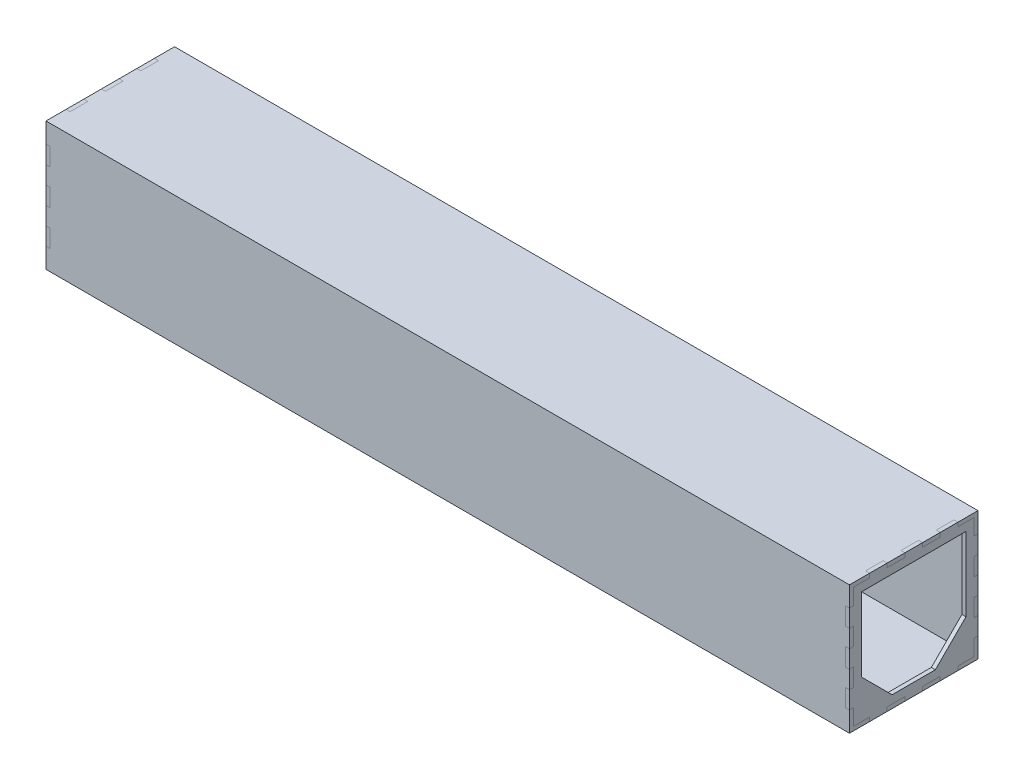
SolidWorks part; units mm, degrees
ref_plane "Front Plane" through (0, 0, 0) normal (0, 0, 1) x (1, 0, 0)
ref_plane "Top Plane" through (0, 0, 0) normal (0, 1, 0) x (1, 0, 0)
ref_plane "Right Plane" through (0, 0, 0) normal (1, 0, 0) x (0, 0, -1)
sketch "Sketch1" plane through (0, 0, 0) normal (1, 0, 0) x (0, 0, -1)
  line L0 (-98.425, 3.175) -> (-98.425, 98.425)
  line L1 (0, 0) -> (-101.6, 0)
  line L2 (0, 0) -> (0, 101.6)
  line L3 (0, 101.6) -> (-101.6, 101.6)
  line L4 (-101.6, 0) -> (-101.6, 101.6)
  line L5 (-3.175, 98.425) -> (-98.425, 98.425)
  line L6 (-3.175, 3.175) -> (-3.175, 98.425)
  line L7 (-3.175, 3.175) -> (-98.425, 3.175)
  dimension "D1" = 101.6
  dimension "D2" = 101.6
  dimension "D3" = 3.175
extrude "Boss-Extrude1" add sketch "Sketch1" along normal blind 628.65
sketch "Sketch3" plane through (0, 0, 0) normal (-1, 0, 0) x (0, 0, 1)
  line L0 (0, 85.725) -> (3.175, 85.725)
  line L1 (0, 0) -> (0, 101.6) construction
  line L2 (3.175, 3.175) -> (3.175, 98.425) construction
  line L3 (15.875, 101.6) -> (15.875, 98.425)
  line L4 (0, 101.6) -> (101.6, 101.6) construction
  line L5 (3.175, 98.425) -> (98.425, 98.425) construction
  line L6 (3.175, 50.8) -> (50.8, 50.8) construction
  line L7 (29.845, 101.6) -> (29.845, 98.425)
  line L8 (43.815, 101.6) -> (43.815, 98.425)
  line L9 (3.175, 98.425) -> (50.8, 50.8) construction
  line L10 (50.8, 50.8) -> (50.8, 98.425) construction
  line L11 (0, 57.785) -> (3.175, 57.785)
  line L12 (0, 71.755) -> (3.175, 71.755)
  line L13 (0, 85.725) -> (0, 101.6)
  line L14 (0, 101.6) -> (15.875, 101.6)
  line L15 (3.175, 85.725) -> (3.175, 98.425)
  line L16 (3.175, 98.425) -> (15.875, 98.425)
  line L17 (29.845, 101.6) -> (43.815, 101.6)
  line L18 (29.845, 98.425) -> (43.815, 98.425)
  line L19 (0, 71.755) -> (0, 57.785)
  line L20 (3.175, 71.755) -> (3.175, 57.785)
  line L21 (98.425, 71.755) -> (98.425, 57.785)
  line L22 (101.6, 71.755) -> (101.6, 57.785)
  line L23 (71.755, 98.425) -> (57.785, 98.425)
  line L24 (71.755, 101.6) -> (57.785, 101.6)
  line L25 (98.425, 98.425) -> (85.725, 98.425)
  line L26 (98.425, 85.725) -> (98.425, 98.425)
  line L27 (101.6, 101.6) -> (85.725, 101.6)
  line L28 (101.6, 85.725) -> (101.6, 101.6)
  line L29 (101.6, 71.755) -> (98.425, 71.755)
  line L30 (101.6, 57.785) -> (98.425, 57.785)
  line L31 (57.785, 101.6) -> (57.785, 98.425)
  line L32 (71.755, 101.6) -> (71.755, 98.425)
  line L33 (85.725, 101.6) -> (85.725, 98.425)
  line L34 (101.6, 85.725) -> (98.425, 85.725)
  line L35 (101.6, 15.875) -> (98.425, 15.875)
  line L36 (85.725, 0) -> (85.725, 3.175)
  line L37 (71.755, 0) -> (71.755, 3.175)
  line L38 (57.785, 0) -> (57.785, 3.175)
  line L39 (101.6, 43.815) -> (98.425, 43.815)
  line L40 (101.6, 29.845) -> (98.425, 29.845)
  line L41 (101.6, 15.875) -> (101.6, 0)
  line L42 (101.6, 0) -> (85.725, 0)
  line L43 (98.425, 15.875) -> (98.425, 3.175)
  line L44 (98.425, 3.175) -> (85.725, 3.175)
  line L45 (71.755, 0) -> (57.785, 0)
  line L46 (71.755, 3.175) -> (57.785, 3.175)
  line L47 (101.6, 29.845) -> (101.6, 43.815)
  line L48 (98.425, 29.845) -> (98.425, 43.815)
  line L49 (3.175, 29.845) -> (3.175, 43.815)
  line L50 (0, 29.845) -> (0, 43.815)
  line L51 (29.845, 3.175) -> (43.815, 3.175)
  line L52 (29.845, 0) -> (43.815, 0)
  line L53 (3.175, 3.175) -> (15.875, 3.175)
  line L54 (3.175, 15.875) -> (3.175, 3.175)
  line L55 (0, 0) -> (15.875, 0)
  line L56 (0, 15.875) -> (0, 0)
  line L57 (0, 29.845) -> (3.175, 29.845)
  line L58 (0, 43.815) -> (3.175, 43.815)
  line L59 (43.815, 0) -> (43.815, 3.175)
  line L60 (29.845, 0) -> (29.845, 3.175)
  line L61 (15.875, 0) -> (15.875, 3.175)
  line L62 (0, 15.875) -> (3.175, 15.875)
  point P27 (50.8, 98.425)
  dimension "D1" = 12.7
  dimension "D2" = 12.7
  dimension "D3" = 13.97
  dimension "D4" = 13.97
  dimension "D5" = 45
extrude "Boss-Extrude3" add sketch "Sketch3" along normal blind 3.175
sketch "Sketch4" plane through (0, 0, 0) normal (-1, 0, 0) x (0, 0, 1)
  line L0 (29.845, 98.425) -> (29.845, 101.6) construction
  line L1 (29.845, 101.6) -> (15.875, 101.6) construction
  line L2 (15.875, 101.6) -> (15.875, 98.425) construction
  line L3 (15.875, 98.425) -> (29.845, 98.425) construction
  line L4 (57.785, 98.425) -> (57.785, 101.6) construction
  line L5 (57.785, 101.6) -> (43.815, 101.6) construction
  line L6 (43.815, 101.6) -> (43.815, 98.425) construction
  line L7 (43.815, 98.425) -> (57.785, 98.425) construction
  line L8 (85.725, 98.425) -> (85.725, 101.6) construction
  line L9 (85.725, 101.6) -> (71.755, 101.6) construction
  line L10 (71.755, 101.6) -> (71.755, 98.425) construction
  line L11 (71.755, 98.425) -> (85.725, 98.425) construction
  line L12 (101.6, 85.725) -> (98.425, 85.725) construction
  line L13 (98.425, 85.725) -> (98.425, 71.755) construction
  line L14 (98.425, 71.755) -> (101.6, 71.755) construction
  line L15 (101.6, 71.755) -> (101.6, 85.725) construction
  line L16 (98.425, 43.815) -> (101.6, 43.815) construction
  line L17 (101.6, 43.815) -> (101.6, 57.785) construction
  line L18 (101.6, 57.785) -> (98.425, 57.785) construction
  line L19 (98.425, 57.785) -> (98.425, 43.815) construction
  line L20 (98.425, 15.875) -> (101.6, 15.875) construction
  line L21 (101.6, 15.875) -> (101.6, 29.845) construction
  line L22 (101.6, 29.845) -> (98.425, 29.845) construction
  line L23 (98.425, 29.845) -> (98.425, 15.875) construction
  line L24 (85.725, 0) -> (85.725, 3.175) construction
  line L25 (85.725, 3.175) -> (71.755, 3.175) construction
  line L26 (71.755, 3.175) -> (71.755, 0) construction
  line L27 (71.755, 0) -> (85.725, 0) construction
  line L28 (57.785, 0) -> (57.785, 3.175) construction
  line L29 (57.785, 3.175) -> (43.815, 3.175) construction
  line L30 (43.815, 3.175) -> (43.815, 0) construction
  line L31 (43.815, 0) -> (57.785, 0) construction
  line L32 (15.875, 3.175) -> (15.875, 0) construction
  line L33 (15.875, 0) -> (29.845, 0) construction
  line L34 (29.845, 0) -> (29.845, 3.175) construction
  line L35 (29.845, 3.175) -> (15.875, 3.175) construction
  line L36 (0, 15.875) -> (3.175, 15.875) construction
  line L37 (3.175, 15.875) -> (3.175, 29.845) construction
  line L38 (3.175, 29.845) -> (0, 29.845) construction
  line L39 (0, 29.845) -> (0, 15.875) construction
  line L40 (3.175, 57.785) -> (0, 57.785) construction
  line L41 (0, 57.785) -> (0, 43.815) construction
  line L42 (0, 43.815) -> (3.175, 43.815) construction
  line L43 (3.175, 43.815) -> (3.175, 57.785) construction
  line L44 (0, 71.755) -> (3.175, 71.755) construction
  line L45 (3.175, 71.755) -> (3.175, 85.725) construction
  line L46 (3.175, 85.725) -> (0, 85.725) construction
  line L47 (0, 85.725) -> (0, 71.755) construction
  line L48 (3.175, 57.785) -> (3.175, 71.755) construction
  line L49 (3.175, 29.845) -> (3.175, 43.815) construction
  line L50 (3.175, 3.175) -> (3.175, 15.875) construction
  line L51 (15.875, 3.175) -> (3.175, 3.175) construction
  line L52 (43.815, 3.175) -> (29.845, 3.175) construction
  line L53 (71.755, 3.175) -> (57.785, 3.175) construction
  line L54 (98.425, 3.175) -> (85.725, 3.175) construction
  line L55 (98.425, 15.875) -> (98.425, 3.175) construction
  line L56 (98.425, 43.815) -> (98.425, 29.845) construction
  line L57 (98.425, 71.755) -> (98.425, 57.785) construction
  line L58 (98.425, 98.425) -> (98.425, 85.725) construction
  line L59 (85.725, 98.425) -> (98.425, 98.425) construction
  line L60 (57.785, 98.425) -> (71.755, 98.425) construction
  line L61 (29.845, 98.425) -> (43.815, 98.425) construction
  line L62 (3.175, 98.425) -> (15.875, 98.425) construction
  line L63 (3.175, 85.725) -> (3.175, 98.425) construction
  line L64 (29.845, 98.425) -> (29.845, 101.6)
  line L65 (29.845, 101.6) -> (15.875, 101.6)
  line L66 (15.875, 101.6) -> (15.875, 98.425)
  line L67 (15.875, 98.425) -> (29.845, 98.425)
  line L68 (57.785, 98.425) -> (57.785, 101.6)
  line L69 (57.785, 101.6) -> (43.815, 101.6)
  line L70 (43.815, 101.6) -> (43.815, 98.425)
  line L71 (43.815, 98.425) -> (57.785, 98.425)
  line L72 (85.725, 98.425) -> (85.725, 101.6)
  line L73 (85.725, 101.6) -> (71.755, 101.6)
  line L74 (71.755, 101.6) -> (71.755, 98.425)
  line L75 (71.755, 98.425) -> (85.725, 98.425)
  line L76 (101.6, 85.725) -> (98.425, 85.725)
  line L77 (98.425, 85.725) -> (98.425, 71.755)
  line L78 (98.425, 71.755) -> (101.6, 71.755)
  line L79 (101.6, 71.755) -> (101.6, 85.725)
  line L80 (98.425, 43.815) -> (101.6, 43.815)
  line L81 (101.6, 43.815) -> (101.6, 57.785)
  line L82 (101.6, 57.785) -> (98.425, 57.785)
  line L83 (98.425, 57.785) -> (98.425, 43.815)
  line L84 (98.425, 15.875) -> (101.6, 15.875)
  line L85 (101.6, 15.875) -> (101.6, 29.845)
  line L86 (101.6, 29.845) -> (98.425, 29.845)
  line L87 (98.425, 29.845) -> (98.425, 15.875)
  line L88 (85.725, 0) -> (85.725, 3.175)
  line L89 (85.725, 3.175) -> (71.755, 3.175)
  line L90 (71.755, 3.175) -> (71.755, 0)
  line L91 (71.755, 0) -> (85.725, 0)
  line L92 (57.785, 0) -> (57.785, 3.175)
  line L93 (57.785, 3.175) -> (43.815, 3.175)
  line L94 (43.815, 3.175) -> (43.815, 0)
  line L95 (43.815, 0) -> (57.785, 0)
  line L96 (15.875, 3.175) -> (15.875, 0)
  line L97 (15.875, 0) -> (29.845, 0)
  line L98 (29.845, 0) -> (29.845, 3.175)
  line L99 (29.845, 3.175) -> (15.875, 3.175)
  line L100 (0, 15.875) -> (3.175, 15.875)
  line L101 (3.175, 15.875) -> (3.175, 29.845)
  line L102 (3.175, 29.845) -> (0, 29.845)
  line L103 (0, 29.845) -> (0, 15.875)
  line L104 (3.175, 57.785) -> (0, 57.785)
  line L105 (0, 57.785) -> (0, 43.815)
  line L106 (0, 43.815) -> (3.175, 43.815)
  line L107 (3.175, 43.815) -> (3.175, 57.785)
  line L108 (0, 71.755) -> (3.175, 71.755)
  line L109 (3.175, 71.755) -> (3.175, 85.725)
  line L110 (3.175, 85.725) -> (0, 85.725)
  line L111 (0, 85.725) -> (0, 71.755)
  line L112 (3.175, 57.785) -> (3.175, 71.755)
  line L113 (3.175, 29.845) -> (3.175, 43.815)
  line L114 (3.175, 3.175) -> (3.175, 15.875)
  line L115 (15.875, 3.175) -> (3.175, 3.175)
  line L116 (43.815, 3.175) -> (29.845, 3.175)
  line L117 (71.755, 3.175) -> (57.785, 3.175)
  line L118 (98.425, 3.175) -> (85.725, 3.175)
  line L119 (98.425, 15.875) -> (98.425, 3.175)
  line L120 (98.425, 43.815) -> (98.425, 29.845)
  line L121 (98.425, 71.755) -> (98.425, 57.785)
  line L122 (98.425, 98.425) -> (98.425, 85.725)
  line L123 (85.725, 98.425) -> (98.425, 98.425)
  line L124 (57.785, 98.425) -> (71.755, 98.425)
  line L125 (29.845, 98.425) -> (43.815, 98.425)
  line L126 (3.175, 98.425) -> (15.875, 98.425)
  line L127 (3.175, 85.725) -> (3.175, 98.425)
  line L129 (3.175, 98.425) -> (98.425, 98.425)
  line L130 (3.175, 98.425) -> (3.175, 3.175)
  line L131 (3.175, 3.175) -> (98.425, 3.175)
  line L132 (98.425, 98.425) -> (98.425, 3.175)
  line M5 (0, 71.755) -> (3.175, 71.755)
  line M6 (3.175, 71.755) -> (3.175, 85.725)
  line M7 (3.175, 85.725) -> (0, 85.725)
  line M8 (0, 85.725) -> (0, 71.755)
extrude "Boss-Extrude4" add sketch "Sketch4" along normal blind 3.175 separate body contours L66 L67 L64 L65 | L127 L112 L107 L113 L101 L114 L115 L99 L116 L93 L117 L89 L118 L119 L87 L120 L83 L121 L77 L122 L123 L75 L124 L71 L125 L67 L126 M6 | L70 L71 L68 L69 | L74 L75 L72 L73 | L78 L79 L76 L77 | L82 L83 L80 L81 | L86 L87 L84 L85 | L90 L91 L88 L89 | L94 L95 L92 L93 | L98 L99 L96 L97 | L102 L103 L100 L101 | L106 L107 L104 L105 | M8 M5 M6 M7 region at (0, 100.0125, 22.86) region at (0, 50.8, 50.8) region at (0, 100.0125, 50.8) region at (0, 78.74, 1.5875) region at (0, 100.0125, 78.74) region at (0, 50.8, 1.5875) region at (0, 78.74, 100.0125) region at (0, 22.86, 1.5875) region at (0, 50.8, 100.0125) region at (0, 1.5875, 22.86) region at (0, 22.86, 100.0125) region at (0, 1.5875, 50.8) region at (0, 1.5875, 78.74)
sketch "Sketch5" plane through (628.65, 0, 0) normal (1, 0, 0) x (0, 0, -1)
  line L0 (-92.075, 33.7033) -> (-67.8967, 9.525)
  line L1 (-92.075, 92.075) -> (-9.525, 92.075)
  line L2 (-92.075, 92.075) -> (-92.075, 9.525) construction
  line L3 (-92.075, 9.525) -> (-9.525, 9.525) construction
  line L4 (-9.525, 92.075) -> (-9.525, 9.525) construction
  line L5 (-33.7033, 9.525) -> (-9.525, 33.7033)
  line L6 (-67.8967, 9.525) -> (-33.7033, 9.525)
  line L7 (-92.075, 33.7033) -> (-92.075, 92.075)
  line L8 (-9.525, 92.075) -> (-9.525, 33.7033)
  line L52 (-15.875, 98.425) -> (-15.875, 101.6)
  line L53 (-3.175, 98.425) -> (-15.875, 98.425)
  line L54 (-3.175, 85.725) -> (-3.175, 98.425)
  line L55 (0, 85.725) -> (-3.175, 85.725)
  line L56 (0, 71.755) -> (0, 85.725)
  line L57 (-3.175, 71.755) -> (0, 71.755)
  line L58 (-3.175, 57.785) -> (-3.175, 71.755)
  line L59 (0, 57.785) -> (-3.175, 57.785)
  line L60 (0, 43.815) -> (0, 57.785)
  line L61 (-3.175, 43.815) -> (0, 43.815)
  line L62 (-3.175, 29.845) -> (-3.175, 43.815)
  line L63 (0, 29.845) -> (-3.175, 29.845)
  line L64 (0, 15.875) -> (0, 29.845)
  line L65 (-3.175, 15.875) -> (0, 15.875)
  line L66 (-3.175, 3.175) -> (-3.175, 15.875)
  line L67 (-15.875, 3.175) -> (-3.175, 3.175)
  line L68 (-15.875, 0) -> (-15.875, 3.175)
  line L69 (-29.845, 0) -> (-15.875, 0)
  line L70 (-29.845, 3.175) -> (-29.845, 0)
  line L71 (-43.815, 3.175) -> (-29.845, 3.175)
  line L72 (-43.815, 0) -> (-43.815, 3.175)
  line L73 (-57.785, 0) -> (-43.815, 0)
  line L74 (-57.785, 3.175) -> (-57.785, 0)
  line L75 (-71.755, 3.175) -> (-57.785, 3.175)
  line L76 (-71.755, 0) -> (-71.755, 3.175)
  line L77 (-85.725, 0) -> (-71.755, 0)
  line L78 (-85.725, 3.175) -> (-85.725, 0)
  line L79 (-98.425, 3.175) -> (-85.725, 3.175)
  line L80 (-98.425, 15.875) -> (-98.425, 3.175)
  line L81 (-101.6, 15.875) -> (-98.425, 15.875)
  line L82 (-101.6, 29.845) -> (-101.6, 15.875)
  line L83 (-98.425, 29.845) -> (-101.6, 29.845)
  line L84 (-98.425, 43.815) -> (-98.425, 29.845)
  line L85 (-101.6, 43.815) -> (-98.425, 43.815)
  line L86 (-101.6, 57.785) -> (-101.6, 43.815)
  line L87 (-98.425, 57.785) -> (-101.6, 57.785)
  line L88 (-98.425, 71.755) -> (-98.425, 57.785)
  line L89 (-101.6, 71.755) -> (-98.425, 71.755)
  line L90 (-101.6, 85.725) -> (-101.6, 71.755)
  line L91 (-98.425, 85.725) -> (-101.6, 85.725)
  line L92 (-98.425, 98.425) -> (-98.425, 85.725)
  line L93 (-85.725, 98.425) -> (-98.425, 98.425)
  line L94 (-85.725, 101.6) -> (-85.725, 98.425)
  line L95 (-71.755, 101.6) -> (-85.725, 101.6)
  line L96 (-71.755, 98.425) -> (-71.755, 101.6)
  line L97 (-57.785, 98.425) -> (-71.755, 98.425)
  line L98 (-57.785, 101.6) -> (-57.785, 98.425)
  line L99 (-43.815, 101.6) -> (-57.785, 101.6)
  line L100 (-43.815, 98.425) -> (-43.815, 101.6)
  line L101 (-29.845, 98.425) -> (-43.815, 98.425)
  line L102 (-29.845, 101.6) -> (-29.845, 98.425)
  line L103 (-15.875, 101.6) -> (-29.845, 101.6)
  line L104 (-15.875, 98.425) -> (-15.875, 101.6)
  line L105 (-3.175, 98.425) -> (-15.875, 98.425)
  line L106 (-3.175, 85.725) -> (-3.175, 98.425)
  line L107 (0, 85.725) -> (-3.175, 85.725)
  line L108 (0, 71.755) -> (0, 85.725)
  line L109 (-3.175, 71.755) -> (0, 71.755)
  line L110 (-3.175, 57.785) -> (-3.175, 71.755)
  line L111 (0, 57.785) -> (-3.175, 57.785)
  line L112 (0, 43.815) -> (0, 57.785)
  line L113 (-3.175, 43.815) -> (0, 43.815)
  line L114 (-3.175, 29.845) -> (-3.175, 43.815)
  line L115 (0, 29.845) -> (-3.175, 29.845)
  line L116 (0, 15.875) -> (0, 29.845)
  line L117 (-3.175, 15.875) -> (0, 15.875)
  line L118 (-3.175, 3.175) -> (-3.175, 15.875)
  line L119 (-15.875, 3.175) -> (-3.175, 3.175)
  line L120 (-15.875, 0) -> (-15.875, 3.175)
  line L121 (-29.845, 0) -> (-15.875, 0)
  line L122 (-29.845, 3.175) -> (-29.845, 0)
  line L123 (-43.815, 3.175) -> (-29.845, 3.175)
  line L124 (-43.815, 0) -> (-43.815, 3.175)
  line L125 (-57.785, 0) -> (-43.815, 0)
  line L126 (-57.785, 3.175) -> (-57.785, 0)
  line L127 (-71.755, 3.175) -> (-57.785, 3.175)
  line L128 (-71.755, 0) -> (-71.755, 3.175)
  line L129 (-85.725, 0) -> (-71.755, 0)
  line L130 (-85.725, 3.175) -> (-85.725, 0)
  line L131 (-98.425, 3.175) -> (-85.725, 3.175)
  line L132 (-98.425, 15.875) -> (-98.425, 3.175)
  line L133 (-101.6, 15.875) -> (-98.425, 15.875)
  line L134 (-101.6, 29.845) -> (-101.6, 15.875)
  line L135 (-98.425, 29.845) -> (-101.6, 29.845)
  line L136 (-98.425, 43.815) -> (-98.425, 29.845)
  line L137 (-101.6, 43.815) -> (-98.425, 43.815)
  line L138 (-101.6, 57.785) -> (-101.6, 43.815)
  line L139 (-98.425, 57.785) -> (-101.6, 57.785)
  line L140 (-98.425, 71.755) -> (-98.425, 57.785)
  line L141 (-101.6, 71.755) -> (-98.425, 71.755)
  line L142 (-101.6, 85.725) -> (-101.6, 71.755)
  line L143 (-98.425, 85.725) -> (-101.6, 85.725)
  line L144 (-98.425, 98.425) -> (-98.425, 85.725)
  line L145 (-85.725, 98.425) -> (-98.425, 98.425)
  line L146 (-85.725, 101.6) -> (-85.725, 98.425)
  line L147 (-71.755, 101.6) -> (-85.725, 101.6)
  line L148 (-71.755, 98.425) -> (-71.755, 101.6)
  line L149 (-57.785, 98.425) -> (-71.755, 98.425)
  line L150 (-57.785, 101.6) -> (-57.785, 98.425)
  line L151 (-43.815, 101.6) -> (-57.785, 101.6)
  line L152 (-43.815, 98.425) -> (-43.815, 101.6)
  line L153 (-29.845, 98.425) -> (-43.815, 98.425)
  line L154 (-29.845, 101.6) -> (-29.845, 98.425)
  line L155 (-15.875, 101.6) -> (-29.845, 101.6)
  circle A0 centre (-50.8, 50.8) radius 41.275
  line M56 (0, 0) -> (0, 101.6)
  line M57 (0, 101.6) -> (-101.6, 101.6)
  line M58 (-101.6, 101.6) -> (-101.6, 0)
  line M59 (-101.6, 0) -> (0, 0)
  line M60 (-3.175, 98.425) -> (-3.175, 3.175)
  line M61 (-3.175, 3.175) -> (-98.425, 3.175)
  line M62 (-98.425, 3.175) -> (-98.425, 98.425)
  line M63 (-98.425, 98.425) -> (-3.175, 98.425)
  dimension "D2" = 82.55
  dimension "D3" = 82.55
  dimension "D4" = 6.35
  dimension "D5" = 6.35
  dimension "D6" = 45
  dimension "D7" = 45
  dimension "D1" = 0
extrude "Boss-Extrude5" add sketch "Sketch5" along normal blind 3.175 separate body contours L1 L8 L5 L6 L0 L7 M60 M63 M62 M61 | L135 L133 M62 M58 | L139 L137 M62 M58 | L143 L141 M62 M58 | L148 L146 M63 M57 | L152 L150 M63 M57 | L154 L104 M57 M63 | L109 L107 M60 M56 | L113 L111 M60 M56 | L117 L115 M60 M56 | L122 L120 M61 M59 | L126 L124 M61 M59 | L130 L128 M61 M59 region at (628.65, 100.0125, 22.86) region at (628.65, 97.078, 9.525) region at (628.65, 78.74, 1.5875) region at (628.65, 100.0125, 50.8) region at (628.65, 50.8, 1.5875) region at (628.65, 100.0125, 78.74) region at (628.65, 22.86, 1.5875) region at (628.65, 78.74, 100.0125) region at (628.65, 1.5875, 22.86) region at (628.65, 50.8, 100.0125) region at (628.65, 1.5875, 50.8) region at (628.65, 22.86, 100.0125) region at (628.65, 1.5875, 78.74)
sketch "Sketch6" plane through (628.65, 0, 0) normal (1, 0, 0) x (0, 0, -1)
  line L0 (-101.6, 29.845) -> (-101.6, 43.815) construction
  line L1 (-101.6, 43.815) -> (-98.425, 43.815) construction
  line L2 (-98.425, 43.815) -> (-98.425, 29.845) construction
  line L3 (-98.425, 29.845) -> (-101.6, 29.845) construction
  line L4 (-101.6, 71.755) -> (-98.425, 71.755) construction
  line L5 (-98.425, 71.755) -> (-98.425, 57.785) construction
  line L6 (-98.425, 57.785) -> (-101.6, 57.785) construction
  line L7 (-101.6, 57.785) -> (-101.6, 71.755) construction
  line L8 (-98.425, 98.425) -> (-98.425, 85.725) construction
  line L9 (-98.425, 85.725) -> (-101.6, 85.725) construction
  line L10 (-101.6, 85.725) -> (-101.6, 101.6) construction
  line L11 (-101.6, 101.6) -> (-85.725, 101.6) construction
  line L12 (-85.725, 101.6) -> (-85.725, 98.425) construction
  line L13 (-85.725, 98.425) -> (-98.425, 98.425) construction
  line L14 (-71.755, 98.425) -> (-71.755, 101.6) construction
  line L15 (-71.755, 101.6) -> (-57.785, 101.6) construction
  line L16 (-57.785, 101.6) -> (-57.785, 98.425) construction
  line L17 (-57.785, 98.425) -> (-71.755, 98.425) construction
  line L18 (-43.815, 101.6) -> (-29.845, 101.6) construction
  line L19 (-29.845, 101.6) -> (-29.845, 98.425) construction
  line L20 (-29.845, 98.425) -> (-43.815, 98.425) construction
  line L21 (-43.815, 98.425) -> (-43.815, 101.6) construction
  line L22 (0, 101.6) -> (0, 85.725) construction
  line L23 (0, 85.725) -> (-3.175, 85.725) construction
  line L24 (-3.175, 85.725) -> (-3.175, 98.425) construction
  line L25 (-3.175, 98.425) -> (-15.875, 98.425) construction
  line L26 (-15.875, 98.425) -> (-15.875, 101.6) construction
  line L27 (-15.875, 101.6) -> (0, 101.6) construction
  line L28 (0, 71.755) -> (0, 57.785) construction
  line L29 (0, 57.785) -> (-3.175, 57.785) construction
  line L30 (-3.175, 57.785) -> (-3.175, 71.755) construction
  line L31 (-3.175, 71.755) -> (0, 71.755) construction
  line L32 (0, 29.845) -> (-3.175, 29.845) construction
  line L33 (-3.175, 29.845) -> (-3.175, 43.815) construction
  line L34 (-3.175, 43.815) -> (0, 43.815) construction
  line L35 (0, 43.815) -> (0, 29.845) construction
  line L36 (-3.175, 3.175) -> (-3.175, 15.875) construction
  line L37 (-3.175, 15.875) -> (0, 15.875) construction
  line L38 (0, 15.875) -> (0, 0) construction
  line L39 (0, 0) -> (-15.875, 0) construction
  line L40 (-15.875, 0) -> (-15.875, 3.175) construction
  line L41 (-15.875, 3.175) -> (-3.175, 3.175) construction
  line L42 (-29.845, 3.175) -> (-29.845, 0) construction
  line L43 (-29.845, 0) -> (-43.815, 0) construction
  line L44 (-43.815, 0) -> (-43.815, 3.175) construction
  line L45 (-43.815, 3.175) -> (-29.845, 3.175) construction
  line L46 (-57.785, 0) -> (-71.755, 0) construction
  line L47 (-71.755, 0) -> (-71.755, 3.175) construction
  line L48 (-71.755, 3.175) -> (-57.785, 3.175) construction
  line L49 (-57.785, 3.175) -> (-57.785, 0) construction
  line L50 (-101.6, 0) -> (-101.6, 15.875) construction
  line L51 (-101.6, 15.875) -> (-98.425, 15.875) construction
  line L52 (-98.425, 15.875) -> (-98.425, 3.175) construction
  line L53 (-98.425, 3.175) -> (-85.725, 3.175) construction
  line L54 (-85.725, 3.175) -> (-85.725, 0) construction
  line L55 (-85.725, 0) -> (-101.6, 0) construction
  line L56 (-101.6, 29.845) -> (-101.6, 43.815)
  line L57 (-101.6, 43.815) -> (-98.425, 43.815)
  line L58 (-98.425, 43.815) -> (-98.425, 29.845)
  line L59 (-98.425, 29.845) -> (-101.6, 29.845)
  line L60 (-101.6, 71.755) -> (-98.425, 71.755)
  line L61 (-98.425, 71.755) -> (-98.425, 57.785)
  line L62 (-98.425, 57.785) -> (-101.6, 57.785)
  line L63 (-101.6, 57.785) -> (-101.6, 71.755)
  line L64 (-98.425, 98.425) -> (-98.425, 85.725)
  line L65 (-98.425, 85.725) -> (-101.6, 85.725)
  line L66 (-101.6, 85.725) -> (-101.6, 101.6)
  line L67 (-101.6, 101.6) -> (-85.725, 101.6)
  line L68 (-85.725, 101.6) -> (-85.725, 98.425)
  line L69 (-85.725, 98.425) -> (-98.425, 98.425)
  line L70 (-71.755, 98.425) -> (-71.755, 101.6)
  line L71 (-71.755, 101.6) -> (-57.785, 101.6)
  line L72 (-57.785, 101.6) -> (-57.785, 98.425)
  line L73 (-57.785, 98.425) -> (-71.755, 98.425)
  line L74 (-43.815, 101.6) -> (-29.845, 101.6)
  line L75 (-29.845, 101.6) -> (-29.845, 98.425)
  line L76 (-29.845, 98.425) -> (-43.815, 98.425)
  line L77 (-43.815, 98.425) -> (-43.815, 101.6)
  line L78 (0, 101.6) -> (0, 85.725)
  line L79 (0, 85.725) -> (-3.175, 85.725)
  line L80 (-3.175, 85.725) -> (-3.175, 98.425)
  line L81 (-3.175, 98.425) -> (-15.875, 98.425)
  line L82 (-15.875, 98.425) -> (-15.875, 101.6)
  line L83 (-15.875, 101.6) -> (0, 101.6)
  line L84 (0, 71.755) -> (0, 57.785)
  line L85 (0, 57.785) -> (-3.175, 57.785)
  line L86 (-3.175, 57.785) -> (-3.175, 71.755)
  line L87 (-3.175, 71.755) -> (0, 71.755)
  line L88 (0, 29.845) -> (-3.175, 29.845)
  line L89 (-3.175, 29.845) -> (-3.175, 43.815)
  line L90 (-3.175, 43.815) -> (0, 43.815)
  line L91 (0, 43.815) -> (0, 29.845)
  line L92 (-3.175, 3.175) -> (-3.175, 15.875)
  line L93 (-3.175, 15.875) -> (0, 15.875)
  line L94 (0, 15.875) -> (0, 0)
  line L95 (0, 0) -> (-15.875, 0)
  line L96 (-15.875, 0) -> (-15.875, 3.175)
  line L97 (-15.875, 3.175) -> (-3.175, 3.175)
  line L98 (-29.845, 3.175) -> (-29.845, 0)
  line L99 (-29.845, 0) -> (-43.815, 0)
  line L100 (-43.815, 0) -> (-43.815, 3.175)
  line L101 (-43.815, 3.175) -> (-29.845, 3.175)
  line L102 (-57.785, 0) -> (-71.755, 0)
  line L103 (-71.755, 0) -> (-71.755, 3.175)
  line L104 (-71.755, 3.175) -> (-57.785, 3.175)
  line L105 (-57.785, 3.175) -> (-57.785, 0)
  line L106 (-101.6, 0) -> (-101.6, 15.875)
  line L107 (-101.6, 15.875) -> (-98.425, 15.875)
  line L108 (-98.425, 15.875) -> (-98.425, 3.175)
  line L109 (-98.425, 3.175) -> (-85.725, 3.175)
  line L110 (-85.725, 3.175) -> (-85.725, 0)
  line L111 (-85.725, 0) -> (-101.6, 0)
extrude "Boss-Extrude6" add sketch "Sketch6" along normal blind 3.175
